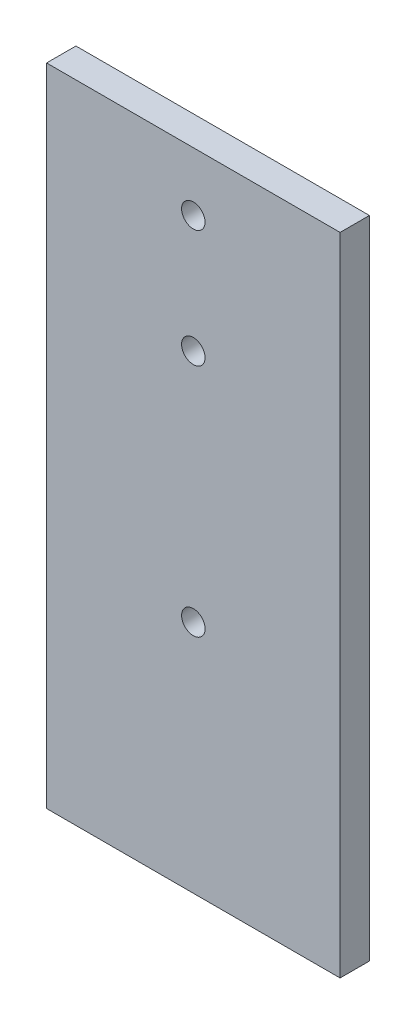
SolidWorks part; units mm, degrees
ref_plane "Plan de face" through (0, 0, 0) normal (0, 0, 1) x (1, 0, 0)
ref_plane "Plan de dessus" through (0, 0, 0) normal (0, 1, 0) x (1, 0, 0)
ref_plane "Plan de droite" through (0, 0, 0) normal (1, 0, 0) x (0, 0, -1)
sketch "Esquisse1" plane through (0, 0, 0) normal (0, 0, 1) x (1, 0, 0)
  line L0 (-25, 0) -> (25, 0) construction
  line L1 (25, 50) -> (25, 0)
  line L2 (25, 0) -> (25, -60)
  line L3 (-25, 50) -> (25, 50)
  line L4 (25, -60) -> (-25, -60)
  line L7 (-25, -60) -> (-25, 0)
  line L8 (0, 50) -> (0, -60) construction
  line L9 (-25, 0) -> (-25, 50)
  circle A0 centre (0, 20) radius 2
  circle A1 centre (0, -20) radius 2
  circle A2 centre (0, 40) radius 2
  point P0 (0, 0)
  point P2 (0, 0)
  dimension "D3" = 4
  dimension "D4" = 4
  dimension "D5" = 20
  dimension "D7" = 4
  dimension "D1" = 50
  dimension "D2" = 25
  dimension "D6" = 20
  dimension "D8" = 40
  dimension "D9" = 60
  dimension "D10" = 25
extrude "Boss.-Extru.1" add sketch "Esquisse1" along normal blind 5
